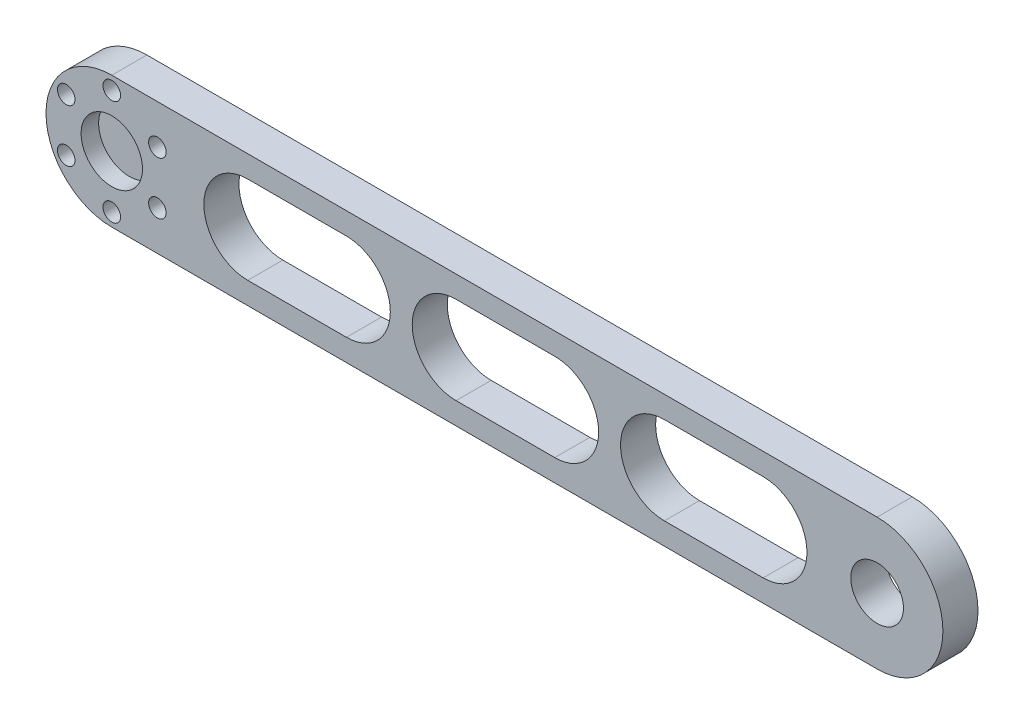
SolidWorks part; units mm, degrees
material "1060 Alloy"
ref_plane "Front Plane" through (0, 0, 0) normal (0, 0, 1) x (1, 0, 0)
ref_plane "Top Plane" through (0, 0, 0) normal (0, 1, 0) x (1, 0, 0)
ref_plane "Right Plane" through (0, 0, 0) normal (1, 0, 0) x (0, 0, -1)
sketch "Sketch1" plane through (0, 0, 0) normal (0, 0, 1) x (1, 0, 0)
  line L0 (-87.25, 0) -> (87.25, 0) construction
  line L1 (55, 0) -> (-55, 0) construction
  line L2 (-87.25, 15) -> (87.25, 15)
  line L3 (-87.25, -15) -> (87.25, -15)
  line L4 (61.25, 0) -> (38.75, 0) construction
  line L5 (61.25, -10) -> (38.75, -10)
  line L6 (61.25, 10) -> (38.75, 10)
  line L7 (13.75, 0) -> (-8.75, 0) construction
  line L8 (13.75, -10) -> (-8.75, -10)
  line L9 (13.75, 10) -> (-8.75, 10)
  line L10 (-33.75, 0) -> (-56.25, 0) construction
  line L11 (-33.75, -10) -> (-56.25, -10)
  line L12 (-33.75, 10) -> (-56.25, 10)
  arc A0 (-87.25, 15) -> (-87.25, -15) centre (-87.25, 0) ccw
  arc A1 (87.25, -15) -> (87.25, 15) centre (87.25, 0) ccw
  circle A2 centre (87.25, 0) radius 6
  arc A3 (61.25, -10) -> (61.25, 10) centre (61.25, 0) ccw
  arc A4 (38.75, 10) -> (38.75, -10) centre (38.75, 0) ccw
  arc A5 (13.75, -10) -> (13.75, 10) centre (13.75, 0) ccw
  arc A6 (-8.75, 10) -> (-8.75, -10) centre (-8.75, 0) ccw
  arc A7 (-33.75, -10) -> (-33.75, 10) centre (-33.75, 0) ccw
  arc A8 (-56.25, 10) -> (-56.25, -10) centre (-56.25, 0) ccw
  point P5 (0, 0)
  point P14 (50, 0)
  point P19 (2.5, 0)
  point P26 (-45, 0)
  dimension "D3" = 15
  dimension "D4" = 12
  dimension "D8" = 10
  dimension "D9" = 10
  dimension "D10" = 10
  dimension "D1" = 174.5
  dimension "D2" = 87.25
  dimension "D5" = 22.5
  dimension "D6" = 22.5
  dimension "D7" = 22.5
  dimension "D11" = 26
  dimension "D12" = 25
  dimension "D13" = 25
extrude "Boss-Extrude1" add sketch "Sketch1" along normal blind 8
sketch "Sketch2" plane through (0, 0, 8) normal (0, 0, 1) x (1, 0, 0)
  circle A0 centre (-87.25, 0) radius 15
  dimension "D1" = 30
extrude "Boss-Extrude3" [suppressed] add sketch "Sketch2" along normal blind 30
ref_plane "Plane1" through (0, 0, 23) normal (0, 0, 1) x (1, 0, 0)
ref_axis "Axis1" through (-87.25, 0, 38) along (0, 0, -1)
hole_wizard "Ø4.0mm Dowel Hole1" positions "Sketch8" profile "Sketch7" hole size "Ø4.0" standard "ISO"
sketch "Sketch8" plane through (0, 0, 0) normal (0, 0, -1) x (-1, 0, 0)
  point P0 (87.25, 12)
  dimension "D1" = 12
sketch "Sketch7" plane through (-87.25, 12, 0) normal (1, 0, 0) x (0, 1, 0)
  line L0 (0, 0) -> (0, 101.2017)
  line L1 (0, 101.2017) -> (2, 100)
  line L2 (2, 100) -> (2, 0)
  line L5 (2, 0) -> (0, 0)
  line L10 (0, 101.2017) -> (-2, 100) construction
  line L11 (0, -6.35) -> (0, 107.95) construction
  dimension "Hole Dia." = 4
  dimension "Hole Depth" = 100
  dimension "Drill Angle" = 118
pattern_circular "CirPattern1" count 6 over 360 about axis through (-87.25, 0, 38) along (0, 0, -1) of "Ø4.0mm Dowel Hole1"
fillet "Fillet3" [suppressed] radius 2.5
ref_plane "Plane2" through (0, 0, 4) normal (0, 0, 1) x (1, 0, 0)
sketch "Sketch9" plane through (0, 0, 8) normal (0, 0, 1) x (1, 0, 0)
  circle A0 centre (-87.25, 0) radius 7
  dimension "D1" = 14
extrude "Cut-Extrude1" cut sketch "Sketch9" against normal blind 4
equation "\"upperlinklength\"=174.5"
equation "\"D1@Sketch1\"=\"upperlinklength\""
equation "\"D2@Sketch1\"=\"upperlinklength\"/2"
equation "\"upperlinkgap\"=22.5"
equation "\"D5@Sketch1\"=\"upperlinkgap\""
equation "\"D6@Sketch1\"=\"upperlinkgap\""
equation "\"D7@Sketch1\"=\"upperlinkgap\""
equation "\"gapwidth\"=10"
equation "\"D8@Sketch1\"=\"gapwidth\""
equation "\"D9@Sketch1\"=\"gapwidth\""
equation "\"D10@Sketch1\"=\"gapwidth\""
